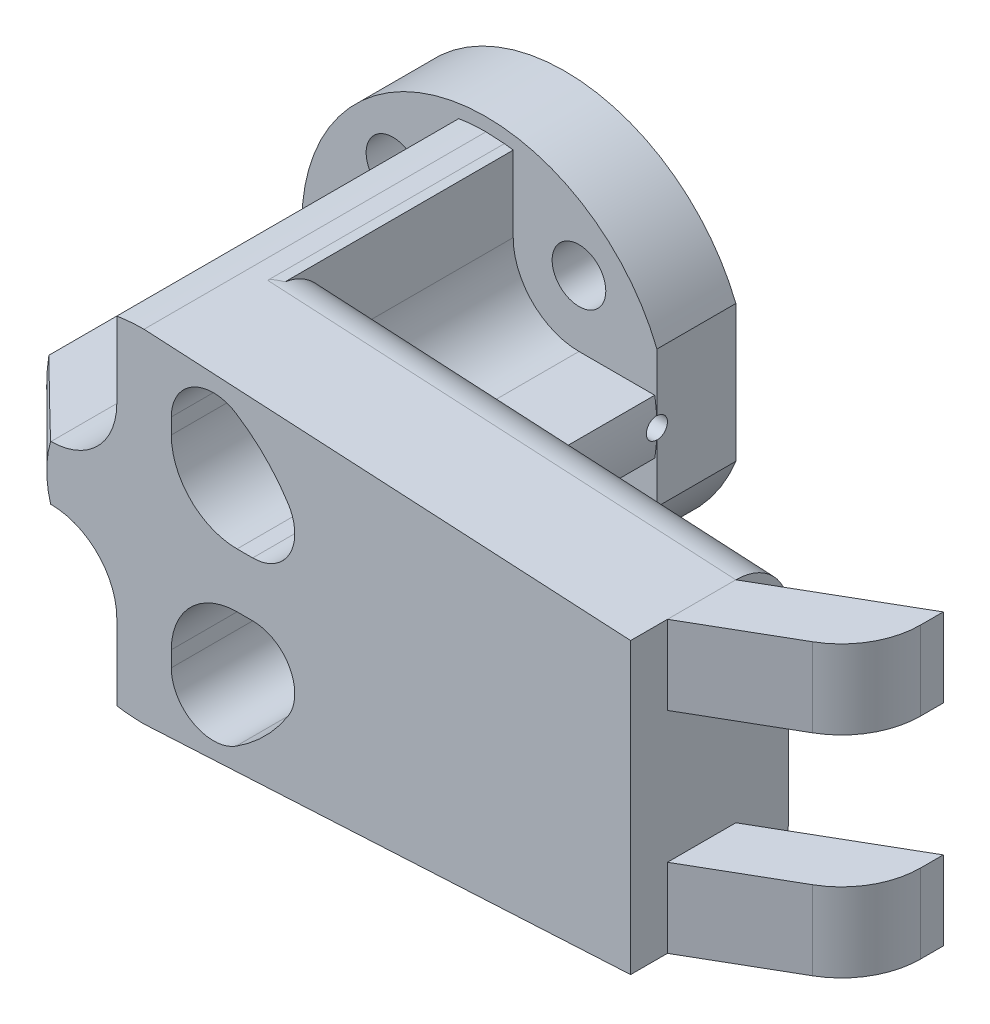
SolidWorks part; units mm, degrees
ref_plane "Front" through (0, 0, 0) normal (0, 0, 1) x (1, 0, 0)
ref_plane "Top" through (0, 0, 0) normal (0, 1, 0) x (1, 0, 0)
ref_plane "Right" through (0, 0, 0) normal (1, 0, 0) x (0, 0, -1)
sketch "Sketch1" plane through (0, 0, 0) normal (0, 0, 1) x (1, 0, 0)
  circle A0 centre (0, 0) radius 35
  dimension "D1" = 70
extrude "Boss-Extrude1" add sketch "Sketch1" along normal blind 80
sketch "Sketch2" plane through (0, 0, 80) normal (0, 0, 1) x (1, 0, 0)
  line L1 (-17.68, 17.68) -> (17.68, 17.68) construction
  line L2 (-17.68, 17.68) -> (-17.68, -17.68) construction
  line L3 (-17.68, -17.68) -> (17.68, -17.68) construction
  line L4 (17.68, 17.68) -> (17.68, -17.68) construction
  line L5 (-17.68, 17.68) -> (17.68, -17.68) construction
  line L6 (-17.68, -17.68) -> (17.68, 17.68) construction
  circle A0 centre (17.68, -17.68) radius 5.1
  circle A1 centre (17.68, 17.68) radius 5.1
  circle A2 centre (-17.68, 17.68) radius 5.1
  circle A3 centre (-17.68, -17.68) radius 5.1
  point P0 (0, 0)
  dimension "D1" = 10.2
  dimension "D2" = 35.36
  dimension "D3" = 35.36
extrude "Cut-Extrude1" cut sketch "Sketch2" against normal up to next from offset 50 offset against normal yes
sketch "Sketch16" plane through (0, 0, 80) normal (0, 0, 1) x (1, 0, 0)
  circle A0 centre (0, 0) radius 32.5
  circle A1 centre (0, 0) radius 35
  circle A3 centre (0, 0) radius 35 construction
  dimension "D1" = 65
extrude "Cut-Extrude7" cut sketch "Sketch16" against normal blind 65
ref_plane "Plane1" through (32.5, 0, 0) normal (1, 0, 0) x (0, 0, -1)
sketch "Sketch7" plane through (32.5, 0, 0) normal (1, 0, 0) x (0, 0, -1)
  line L1 (-50, 32.5) -> (-80, 32.5)
  line L2 (-50, 32.5) -> (-50, -32.5)
  line L3 (-50, -32.5) -> (-80, -32.5)
  line L4 (-80, 32.5) -> (-80, -32.5)
  line L6 (-15, 32.5) -> (-80, 32.5) construction
  line L8 (-80, 32.5) -> (-80, -32.5) construction
  dimension "D1" = 30
  dimension "D2" = 65
extrude "Boss-Extrude4" add sketch "Sketch7" along normal blind 60 and the other way blind 65
sketch "Sketch17" plane through (0, 0, 50) normal (0, 0, -1) x (-1, 0, 0)
  line L0 (32.5, -32.5) -> (32.5, 0) construction
  line L1 (0, -32.5) -> (32.5, -32.5) construction
  line L2 (32.5, 32.5) -> (0, 32.5) construction
  line L3 (32.5, 0) -> (32.5, 32.5) construction
  line L4 (32.5, -32.5) -> (32.5, 0)
  line L5 (0, -32.5) -> (32.5, -32.5)
  line L6 (32.5, 32.5) -> (0, 32.5)
  line L7 (32.5, 0) -> (32.5, 32.5)
  arc A0 (0, -32.5) -> (32.5, 0) centre (0, 0) ccw construction
  arc A1 (32.5, 0) -> (0, 32.5) centre (0, 0) ccw construction
  arc A2 (0, -32.5) -> (32.5, 0) centre (0, 0) ccw
  arc A3 (32.5, 0) -> (0, 32.5) centre (0, 0) ccw
  line M1 (32.5, 32.5) -> (0, 32.5)
  arc M2 (0, 32.5) -> (32.5, 0) centre (0, 0) cw
  line M3 (32.5, 0) -> (32.5, 32.5)
extrude "Cut-Extrude8" cut sketch "Sketch17" against normal through all contours M3 M1 M2 | A2 L5 L4 region at (-25.2405, -25.2405, 50) region at (-25.2405, 25.2405, 50)
sketch "Sketch12" plane through (0, 32.5, 0) normal (0, 1, 0) x (1, 0, 0)
  line L6 (92.5, -50) -> (92.5, -80) construction
  line L7 (92.5, -60) -> (117.5, -45.5662)
  line L8 (117.5, -45.5662) -> (117.5, -49.906)
  line L9 (110, -62.8964) -> (92.5, -73)
  line L13 (92.5, -60) -> (92.5, -73)
  arc A1 (117.5, -49.906) -> (110, -62.8964) centre (102.5, -49.906) cw
  dimension "D9" = 15
  dimension "D1" = 10
  dimension "D6" = 25
  dimension "D7" = 60
  dimension "D8" = 13
extrude "Boss-Extrude5" add sketch "Sketch12" against normal blind 15 from offset 5 offset against normal yes
mirror "Mirror1" about plane through (0, 0, 0) normal (0, 1, 0) of "Boss-Extrude5"
sketch "Sketch10" plane through (0, 0, 0) normal (0, 0, -1) x (-1, 0, 0)
  line L0 (5.18, 17.68) -> (5.18, 32.0845)
  line L1 (17.68, 5.18) -> (32.0845, 5.18)
  line L5 (-92.5, -32.5) -> (0, -32.5)
  line L6 (-92.5, 32.5) -> (-92.5, -32.5)
  line L7 (0, 32.5) -> (-92.5, 32.5)
  arc A0 (5.18, 17.68) -> (17.68, 5.18) centre (17.68, 17.68) ccw
  arc A2 (0, -32.5) -> (0, 32.5) centre (0, 0) ccw
  arc A3 (32.0845, 5.18) -> (5.18, 32.0845) centre (0, 0) ccw
  dimension "D1" = 25
  dimension "D2" = 0
extrude "Cut-Extrude2" cut sketch "Sketch10" against normal through all from surface starting at face at (32.5, 0, 15)
pattern_circular "CirPattern1" count 4 over 360 about axis through (0, 0, 0) along (0, 0, 1) of "Cut-Extrude2"
sketch "Sketch14" plane through (0, 0, 80) normal (0, 0, 1) x (1, 0, 0)
  line L0 (92.5, 27.5) -> (0, 32.5)
  line L1 (0, 32.5) -> (92.5, 33.5)
  line L2 (92.5, 33.5) -> (92.5, 27.5)
  line L6 (92.5, 32.5) -> (0, 32.5) construction
  line L7 (0, 0) -> (148.4689, 0) construction
  line L8 (92.5, -33.5) -> (92.5, -27.5)
  line L9 (0, -32.5) -> (92.5, -33.5)
  line L10 (92.5, -27.5) -> (0, -32.5)
  line L11 (92.5, 32.5) -> (92.5, -32.5) construction
  dimension "D1" = 1
extrude "Cut-Extrude4" cut sketch "Sketch14" against normal up to surface (65 mm away) up to face at (0, 0, 15)
fillet "Fillet1" radius 10 2 edges at (48.0016, -29.9053, 50) (48.0016, 29.9053, 50)
ref_plane "Plane2" through (102.5, 0, 0) normal (1, 0, 0) x (0, 0, -1)
sketch "Sketch15" plane through (102.5, 0, 0) normal (1, 0, 0) x (0, 0, -1)
  line L0 (0, -35) -> (0, 35) construction
  circle A0 centre (-35, 0) radius 2
  circle A1 centre (-15, 0) radius 2
  dimension "D1" = 20
  dimension "D2" = 15
  dimension "D3" = 4
extrude "Cut-Extrude6" cut sketch "Sketch15" against normal blind 15 and the other way up to surface from offset 70 other way up to face at (35, 0, 0) offset against normal yes
fillet "Fillet2" radius 8 4 edges at (5.18, 32.0845, 69.1804) (32.0845, 5.18, 65) (32.0845, -5.18, 65) (5.18, -32.0845, 69.1804)
sketch "Sketch19" plane through (0, 0, 15) normal (0, 0, 1) x (1, 0, 0)
  line L0 (32.5, 12.9904) -> (32.5, -12.9904)
  circle A0 centre (0, 0) radius 35 construction
  arc A1 (32.0845, -5.18) -> (32.0845, 5.18) centre (0, 0) ccw construction
  arc A2 (32.5, -12.9904) -> (32.5, 12.9904) centre (0, 0) ccw
  arc A3 (32.0845, -5.18) -> (32.0845, 5.18) centre (0, 0) ccw construction
extrude "Cut-Extrude9" cut sketch "Sketch19" against normal through all
chamfer "Chamfer1" distance 14 angle 45 1 edges at (-32.5, 0, 80)
